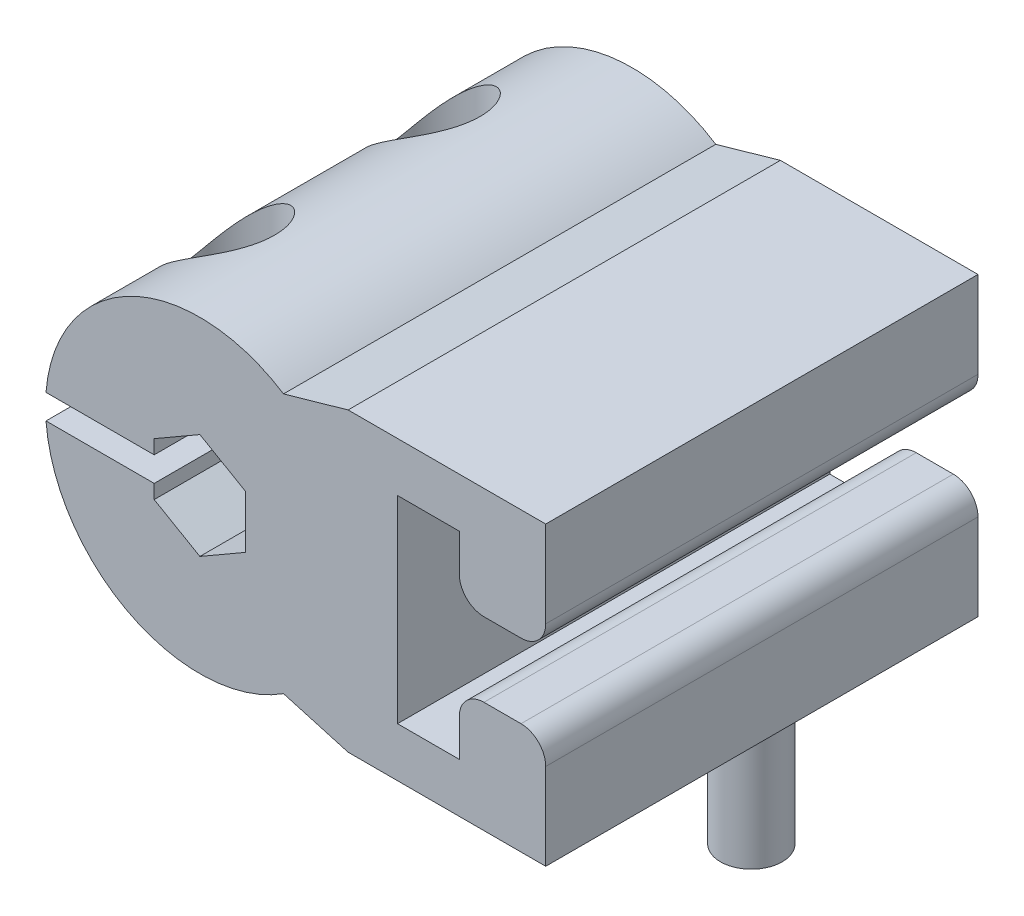
SolidWorks part; units mm, degrees
ref_plane "Front Plane" through (0, 0, 0) normal (0, 0, 1) x (1, 0, 0)
ref_plane "Top Plane" through (0, 0, 0) normal (0, 1, 0) x (1, 0, 0)
ref_plane "Right Plane" through (0, 0, 0) normal (1, 0, 0) x (0, 0, -1)
sketch "Sketch1" plane through (0, 0, 0) normal (0, 0, 1) x (1, 0, 0)
  line L0 (-20.2969, 1) -> (-3.7, 1)
  line L1 (-3.7, 2.1362) -> (-3.7, 1)
  line L2 (-3.7, -2.1362) -> (0, -4.2724)
  line L3 (0, -4.2724) -> (3.7, -2.1362)
  line L4 (3.7, -2.1362) -> (3.7, 2.1362)
  line L5 (3.7, 2.1362) -> (0, 4.2724)
  line L6 (0, 4.2724) -> (-3.7, 2.1362)
  line L7 (-3.7, 0) -> (-22.8855, 0) construction
  line L8 (-20.2969, -1) -> (-3.7, -1)
  line L9 (-20.2969, 1) -> (-20.2969, -1)
  line L10 (-3.7, -1) -> (-3.7, -2.1362)
  arc A0 (-1.85, -3.2043) -> (-1.85, 3.2043) centre (0, 0) ccw construction
  circle A1 centre (0, 0) radius 12.5
  dimension "D2" = 25
  dimension "D1" = 7.4
  dimension "D3" = 1
extrude "Boss-Extrude1" add sketch "Sketch1" along normal blind 35 contours L8 A1 L0 L1 L6 L5 L4 L3 L2 L10 region at (0.4863, 12.137, 0)
ref_plane "Plane1" through (0, 12.5, 0) normal (0, 1, 0) x (1, 0, 0)
sketch "Sketch2" plane through (0, 12.5, 0) normal (0, 1, 0) x (1, 0, 0)
  line L0 (-12.4599, 0) -> (-7.0788, -9.1755) construction
  line L1 (-7.0788, -9.1755) -> (-7.0788, -25.8245) construction
  line L2 (-7.0788, -25.8245) -> (-12.4599, -35) construction
  circle A0 centre (-7.0788, -9.1755) radius 1.8669
  circle A1 centre (-7.0788, -25.8245) radius 1.8669
  dimension "D1" = 3.7338
extrude "Cut-Extrude1" cut sketch "Sketch2" against normal through all
sketch "Sketch3" plane through (0, 12.5, 0) normal (0, 1, 0) x (1, 0, 0)
  circle A0 centre (-7.0788, -9.1755) radius 3.9497
  circle A1 centre (-7.0788, -25.8245) radius 3.9497
  dimension "D1" = 7.8994
extrude "Cut-Extrude2" cut sketch "Sketch3" against normal blind 8
ref_plane "Plane2" through (0, -12.5, 0) normal (0, -1, 0) x (-1, 0, 0)
sketch "Sketch4" plane through (0, -12.5, 0) normal (0, -1, 0) x (-1, 0, 0)
  line L1 (7.0788, -5.2307) -> (3.6625, -7.2031)
  line L2 (3.6625, -7.2031) -> (3.6625, -11.1479)
  line L3 (3.6625, -11.1479) -> (7.0788, -13.1203)
  line L4 (7.0788, -13.1203) -> (10.4951, -11.1479)
  line L5 (10.4951, -11.1479) -> (10.4951, -7.2031)
  line L6 (10.4951, -7.2031) -> (7.0788, -5.2307)
  line L7 (7.0788, -21.8797) -> (3.6625, -23.8521)
  line L8 (3.6625, -23.8521) -> (3.6625, -27.7969)
  line L9 (3.6625, -27.7969) -> (7.0788, -29.7693)
  line L10 (7.0788, -29.7693) -> (10.4951, -27.7969)
  line L11 (10.4951, -27.7969) -> (10.4951, -23.8521)
  line L12 (10.4951, -23.8521) -> (7.0788, -21.8797)
  circle A0 centre (7.0788, -9.1755) radius 3.4163 construction
  circle A1 centre (7.0788, -25.8245) radius 3.4163 construction
  dimension "D1" = 6.8326
extrude "Cut-Extrude3" cut sketch "Sketch4" against normal blind 8
sketch "Sketch5" plane through (0, 0, 0) normal (0, 0, -1) x (-1, 0, 0)
  line L0 (-12, 12) -> (-6.7683, 10.509)
  line L5 (-12, -12) -> (-6.7683, -10.509)
  line L6 (-21, 3) -> (-21, 8)
  line L19 (-12, -12) -> (-28, -12)
  line L21 (-12, 12) -> (-28, 12)
  line L22 (-28, -12) -> (-28, -3)
  line L23 (-16, -8) -> (-21, -8)
  line L24 (-16, -8) -> (-16, 8)
  line L25 (-16, 8) -> (-21, 8)
  line L26 (-21, -8) -> (-21, -3)
  line L27 (-21, -3) -> (-28, -3)
  line L29 (-21, 3) -> (-28, 3)
  line L31 (-28, 3) -> (-28, 12)
  line L34 (0, 12.5) -> (0, -12.5) construction
  arc A0 (12.4599, 1) -> (12.4599, -1) centre (0, 0) ccw construction
  arc A1 (-6.7683, 10.509) -> (-6.7683, -10.509) centre (0, 0) ccw
  dimension "D5" = 7
  dimension "D1" = 16
  dimension "D2" = 24
  dimension "D3" = 6
  dimension "D6" = 12
  dimension "D7" = 28
extrude "Boss-Extrude2" add sketch "Sketch5" against normal through all
fillet "Fillet1" radius 2 4 edges at (21, -3, 17.5) (21, 3, 17.5) (28, 3, 17.5) (28, -3, 17.5)
sketch "Sketch6" plane through (0, -12, 0) normal (0, -1, 0) x (1, 0, 0)
  circle A0 centre (21.7627, 12.1144) radius 2.5
  dimension "D1" = 5
extrude "Boss-Extrude3" add sketch "Sketch6" along normal blind 13
fillet "Fillet2" radius 2 1 edges at (21.7627, -12, 9.6144)
